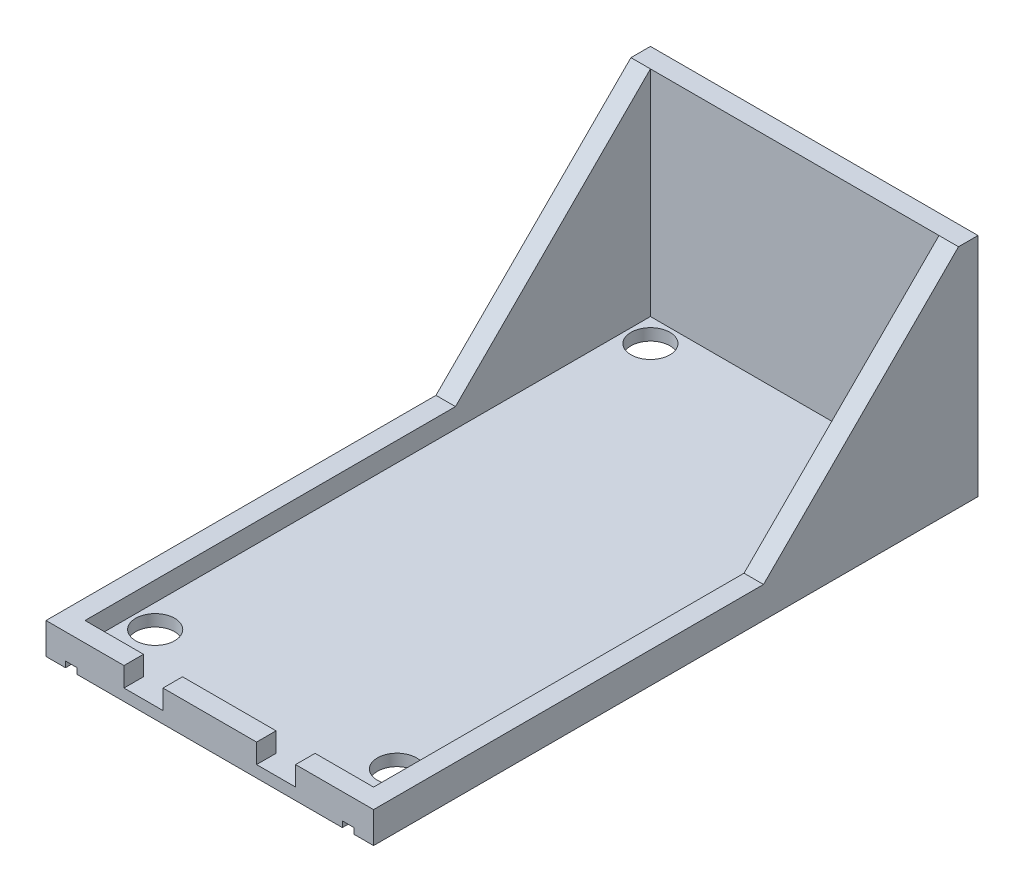
SolidWorks part; units mm, degrees
ref_plane "Front Plane" through (0, 0, 0) normal (0, 0, 1) x (1, 0, 0)
ref_plane "Top Plane" through (0, 0, 0) normal (0, 1, 0) x (1, 0, 0)
ref_plane "Right Plane" through (0, 0, 0) normal (1, 0, 0) x (0, 0, -1)
sketch "Sketch1" plane through (0, 0, 0) normal (0, 1, 0) x (1, 0, 0)
  line L1 (42, -77.5) -> (-42, -77.5)
  line L2 (42, -77.5) -> (42, 77.5)
  line L3 (42, 77.5) -> (-42, 77.5)
  line L4 (-42, -77.5) -> (-42, 77.5)
  line L5 (42, -77.5) -> (-42, 77.5) construction
  line L6 (42, 77.5) -> (-42, -77.5) construction
  point P0 (0, 0)
  dimension "D1" = 84
  dimension "D2" = 155
extrude "Boss-Extrude1" add sketch "Sketch1" along normal blind 3
sketch "Sketch2" plane through (0, 3, 0) normal (0, 1, 0) x (1, 0, 0)
  line L0 (42, -77.5) -> (42, 77.5) construction
  line L1 (37, -72.5) -> (34, -72.5)
  line L2 (37, -72.5) -> (37, -69.5)
  line L3 (37, -69.5) -> (34, -69.5)
  line L4 (34, -72.5) -> (34, -69.5)
  line L5 (-42, -77.5) -> (42, -77.5) construction
  line L6 (-42, 77.5) -> (-42, -77.5) construction
  line L7 (-37, -69.5) -> (-34, -69.5)
  line L8 (-37, -69.5) -> (-37, -72.5)
  line L9 (-37, -72.5) -> (-34, -72.5)
  line L10 (-34, -69.5) -> (-34, -72.5)
  dimension "D1" = 5
  dimension "D2" = 5
  dimension "D3" = 3
  dimension "D4" = 3
  dimension "D5" = 5
  dimension "D6" = 5
  dimension "D7" = 3
  dimension "D8" = 3
extrude "Cut-Extrude1" cut sketch "Sketch2" against normal blind 3
sketch "Sketch3" plane through (0, 0, 77.5) normal (0, 0, 1) x (1, 0, 0)
  line L0 (-42, 3) -> (42, 3) construction
  line L1 (42, 0) -> (37, 0)
  line L2 (42, 0) -> (42, 8)
  line L3 (42, 8) -> (37, 8)
  line L4 (37, 0) -> (37, 8)
  dimension "D1" = 5
  dimension "D2" = 5
extrude "Boss-Extrude2" add sketch "Sketch3" against normal blind 155
sketch "Sketch4" plane through (0, 0, 77.5) normal (0, 0, 1) x (1, 0, 0)
  line L0 (-42, 3) -> (37, 3) construction
  line L1 (-42, 0) -> (-37, 0)
  line L2 (-42, 0) -> (-42, 8)
  line L3 (-42, 8) -> (-37, 8)
  line L4 (-37, 0) -> (-37, 8)
  dimension "D1" = 5
  dimension "D2" = 5
extrude "Boss-Extrude3" add sketch "Sketch4" against normal blind 155
sketch "Sketch5" plane through (-42, 0, 0) normal (-1, 0, 0) x (0, 0, 1)
  line L0 (-77.5, 8) -> (77.5, 8) construction
  line L1 (-77.5, 0) -> (-72.5, 0)
  line L2 (-77.5, 0) -> (-77.5, 58)
  line L3 (-77.5, 58) -> (-72.5, 58)
  line L4 (-72.5, 0) -> (-72.5, 58)
  dimension "D1" = 5
  dimension "D2" = 50
extrude "Boss-Extrude4" add sketch "Sketch5" against normal blind 84
sketch "Sketch6" plane through (-42, 0, 0) normal (-1, 0, 0) x (0, 0, 1)
  line L0 (-72.5, 58) -> (-22.5, 8)
  line L1 (-72.5, 8) -> (77.5, 8) construction
  line L2 (-22.5, 8) -> (-74.3, 4.4168)
  line L3 (-74.3, 4.4168) -> (-74.3, 56.2)
  line L4 (-74.3, 56.2) -> (-72.5, 58)
extrude "Boss-Extrude5" add sketch "Sketch6" against normal blind 5
sketch "Sketch7" plane through (42, 0, 0) normal (1, 0, 0) x (0, 0, -1)
  line L0 (72.5, 58) -> (19.1089, 4.6089)
  line L1 (19.1089, 4.6089) -> (75.2476, 4.6089)
  line L2 (75.2476, 4.6089) -> (75.2476, 53.9164)
  line L3 (75.2476, 53.9164) -> (72.5, 58)
extrude "Boss-Extrude6" add sketch "Sketch7" against normal blind 5
sketch "Sketch8" plane through (0, 0, 77.5) normal (0, 0, 1) x (1, 0, 0)
  line L1 (42, 0) -> (-42, 0)
  line L2 (42, 0) -> (42, 8)
  line L3 (42, 8) -> (-42, 8)
  line L4 (-42, 0) -> (-42, 8)
extrude "Boss-Extrude8" add sketch "Sketch8" against normal blind 5
sketch "Sketch10" plane through (0, 0, 77.5) normal (0, 0, 1) x (1, 0, 0)
  line L0 (-42, 0) -> (42, 0) construction
  line L1 (-22, 3) -> (-12, 3)
  line L2 (-22, 3) -> (-22, 10.4972)
  line L3 (-22, 10.4972) -> (-12, 10.4972)
  line L4 (-12, 3) -> (-12, 10.4972)
  line L5 (-42, 8) -> (-42, 0) construction
  dimension "D1" = 3
  dimension "D2" = 20
  dimension "D3" = 10
extrude "Cut-Extrude2" cut sketch "Sketch10" against normal blind 5
sketch "Sketch11" plane through (0, 0, 77.5) normal (0, 0, 1) x (1, 0, 0)
  line L0 (42, 8) -> (42, 0) construction
  line L1 (22, 3) -> (12, 3)
  line L2 (22, 3) -> (22, 13.6666)
  line L3 (22, 13.6666) -> (12, 13.6666)
  line L4 (12, 3) -> (12, 13.6666)
  line L5 (-42, 0) -> (42, 0) construction
  dimension "D1" = 10
  dimension "D2" = 20
  dimension "D3" = 3
extrude "Cut-Extrude3" cut sketch "Sketch11" against normal blind 5
sketch "Sketch12" plane through (0, 0, 0) normal (0, -1, 0) x (-1, 0, 0)
  line L0 (42, -77.5) -> (-42, -77.5) construction
  line L1 (37, -72.5) -> (34.0087, -72.5)
  line L2 (37, -72.5) -> (37, -77.5)
  line L3 (37, -77.5) -> (34.0087, -77.5)
  line L4 (34.0087, -72.5) -> (34.0087, -77.5)
extrude "Cut-Extrude4" cut sketch "Sketch12" against normal blind 1.5
sketch "Sketch13" plane through (0, 0, 0) normal (0, -1, 0) x (-1, 0, 0)
  line L0 (-34, -72.5) -> (-34, -80.1939)
  line L1 (-37, -72.5) -> (-37, -80.0754)
  line L2 (-37, -80.0754) -> (-34, -80.1939)
  line L3 (-34, -72.5) -> (-37, -72.5)
extrude "Cut-Extrude5" cut sketch "Sketch13" against normal blind 1.5
sketch "Sketch14" plane through (0, 3, 0) normal (0, 1, 0) x (1, 0, 0)
  line L0 (-37, 22.5) -> (-37, 72.5) construction
  line L1 (-37, 72.5) -> (37, 72.5) construction
  circle A0 centre (-31, 66.5) radius 5
  dimension "D1" = 6
  dimension "D2" = 6
extrude "Cut-Extrude6" cut sketch "Sketch14" against normal blind 10
sketch "Sketch15" plane through (0, 3, 0) normal (0, 1, 0) x (1, 0, 0)
  line L0 (37, 72.5) -> (37, -69.5) construction
  line L1 (-37, 72.5) -> (37, 72.5) construction
  circle A0 centre (31, 66.5) radius 5
  dimension "D1" = 6
  dimension "D2" = 6
extrude "Cut-Extrude7" cut sketch "Sketch15" against normal blind 10
sketch "Sketch16" plane through (0, 3, 0) normal (0, 1, 0) x (1, 0, 0)
  line L0 (-37, 22.5) -> (-37, -72.5) construction
  line L1 (-22, -72.5) -> (-37, -72.5) construction
  line L2 (37, 22.5) -> (37, -72.5) construction
  line L3 (37, -72.5) -> (22, -72.5) construction
  circle A0 centre (-31, -60.5) radius 5
  circle A1 centre (31, -60.5) radius 5
  dimension "D1" = 6
  dimension "D2" = 12
  dimension "D3" = 6
  dimension "D4" = 12
extrude "Cut-Extrude8" cut sketch "Sketch16" against normal blind 10
